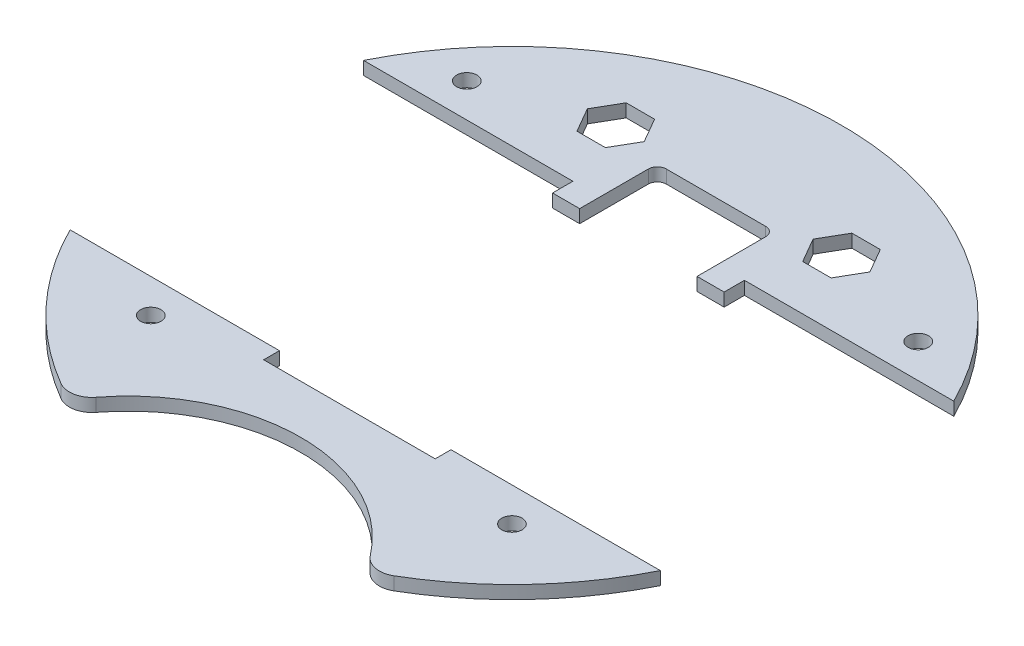
SolidWorks part; units mm, degrees
material "Acrylic (Medium-high impact)"
ref_plane "Front Plane" through (0, 0, 0) normal (0, 0, 1) x (1, 0, 0)
ref_plane "Top Plane" through (0, 0, 0) normal (0, 1, 0) x (1, 0, 0)
ref_plane "Right Plane" through (0, 0, 0) normal (1, 0, 0) x (0, 0, -1)
sketch "Sketch1" plane through (0, 0, 0) normal (0, 1, 0) x (1, 0, 0)
  line L0 (0, -85) -> (-32.7511, -65.2408) construction
  line L1 (0, -85) -> (0, 0) construction
  arc A0 (36.8566, -63.0126) -> (-36.8566, -63.0126) centre (0, 0) ccw
  arc A1 (30.3631, -61.7375) -> (-30.3631, -61.7375) centre (0, -85) ccw
  arc A2 (36.8566, -63.0126) -> (30.3631, -61.7375) centre (34.3322, -58.6967) cw
  arc A3 (-30.3631, -61.7375) -> (-36.8566, -63.0126) centre (-34.3322, -58.6967) cw
  dimension "D1" = 146
  dimension "D2" = 76.5
  dimension "D4" = 5
  dimension "D3" = 85
extrude "Boss-Extrude1" add sketch "Sketch1" along normal blind 2.9
sketch "solenoid placement" plane through (0, 2.9, 0) normal (0, 1, 0) x (1, 0, 0)
  line L4 (-19, -36) -> (19, -36)
  line L5 (-19, 28) -> (-19, -36)
  line L6 (19, 28) -> (-19, 28)
  line L7 (19, -36) -> (19, 28)
  line L8 (-19, -36) -> (19, -36)
  line L9 (-19, 28) -> (-19, -36)
  line L10 (19, 28) -> (-19, 28)
  line L11 (19, -36) -> (19, 28)
  dimension "D1" = 0
extrude "Cut-Extrude1" cut sketch "solenoid placement" against normal through all
sketch "Sketch5" plane through (0, 2.9, 0) normal (0, 1, 0) x (1, 0, 0)
  line L6 (-18.7069, 48) -> (-21.8534, 53.45)
  line L7 (-21.8534, 53.45) -> (-28.1466, 53.45)
  line L8 (-28.1466, 53.45) -> (-31.2931, 48)
  line L9 (-31.2931, 48) -> (-28.1466, 42.55)
  line L10 (-28.1466, 42.55) -> (-21.8534, 42.55)
  line L11 (-21.8534, 42.55) -> (-18.7069, 48)
  line L12 (-18.7069, 48) -> (-21.8534, 53.45)
  line L13 (-21.8534, 53.45) -> (-28.1466, 53.45)
  line L14 (-28.1466, 53.45) -> (-31.2931, 48)
  line L15 (-31.2931, 48) -> (-28.1466, 42.55)
  line L16 (-28.1466, 42.55) -> (-21.8534, 42.55)
  line L17 (-21.8534, 42.55) -> (-18.7069, 48)
  line L18 (18.7069, 48) -> (21.8534, 42.55)
  line L19 (21.8534, 53.45) -> (18.7069, 48)
  line L20 (28.1466, 53.45) -> (21.8534, 53.45)
  line L21 (31.2931, 48) -> (28.1466, 53.45)
  line L22 (28.1466, 42.55) -> (31.2931, 48)
  line L23 (21.8534, 42.55) -> (28.1466, 42.55)
  line L24 (18.7069, 48) -> (21.8534, 42.55)
  line L25 (21.8534, 53.45) -> (18.7069, 48)
  line L26 (28.1466, 53.45) -> (21.8534, 53.45)
  line L27 (31.2931, 48) -> (28.1466, 53.45)
  line L28 (28.1466, 42.55) -> (31.2931, 48)
  line L29 (21.8534, 42.55) -> (28.1466, 42.55)
  dimension "D1" = 0
  dimension "D2" = 0
extrude "Cut-Extrude5" cut sketch "Sketch5" against normal through all
sketch "Sketch6" plane through (0, 2.9, 0) normal (0, 1, 0) x (1, 0, 0)
  circle A0 centre (-50, 40) radius 2.25
  circle A1 centre (40, -40) radius 2.4
  circle A2 centre (40, -40) radius 2.4 construction
  circle A3 centre (-40, -40) radius 2.4
  circle A4 centre (-40, -40) radius 2.4 construction
  circle A5 centre (-50, 40) radius 2.4
  circle A6 centre (-50, 40) radius 2.4 construction
  circle A7 centre (50, 40) radius 2.4
  circle A8 centre (50, 40) radius 2.4 construction
  circle A9 centre (50, 40) radius 2.25
  circle A10 centre (40, -40) radius 2.25
  circle A11 centre (-40, -40) radius 2.25
  point P15 (0, 0)
  dimension "D5" = 4.5
extrude "Cut-Extrude6" cut sketch "Sketch6" against normal through all
sketch "Sketch3" plane through (0, 2.9, 0) normal (0, 1, 0) x (1, 0, 0)
  line L0 (-19, 28) -> (-19, 32.5)
  line L1 (73, -32.5) -> (-73, -32.5)
  line L2 (73, -32.5) -> (73, 32.5)
  line L3 (73, 32.5) -> (19, 32.5)
  line L4 (-73, -32.5) -> (-73, 32.5)
  line L5 (73, -32.5) -> (-73, 32.5) construction
  line L6 (73, 32.5) -> (-73, -32.5) construction
  line L7 (-19, 28) -> (19, 28)
  line L8 (19, 28) -> (19, 32.5)
  line L9 (-19, 32.5) -> (-73, 32.5)
  line L10 (-19, 28) -> (-19, -36) construction
  arc A0 (36.8566, -63.0126) -> (-36.8566, -63.0126) centre (0, 0) ccw construction
  point P0 (0, 0)
  point P10 (0, 0)
  point P13 (0, 0)
  point P14 (19, 28)
  point P19 (-19, 28)
  dimension "D1" = 65
extrude "Cut-Extrude3" cut sketch "Sketch3" against normal through all
sketch "Sketch7" plane through (0, 2.9, 0) normal (0, 1, 0) x (1, 0, 0)
  line L4 (-13, 28) -> (13, 28)
  line L5 (13, 28) -> (13, 43.2)
  line L6 (11, 45.2) -> (-11, 45.2)
  line L7 (-13, 43.2) -> (-13, 28)
  line L8 (-13, 28) -> (13, 28)
  line L9 (13, 28) -> (13, 43.2)
  line L10 (11, 45.2) -> (-11, 45.2)
  line L11 (-13, 43.2) -> (-13, 28)
  arc A2 (13, 43.2) -> (11, 45.2) centre (11, 43.2) ccw
  arc A3 (-11, 45.2) -> (-13, 43.2) centre (-11, 43.2) ccw
  arc A4 (13, 43.2) -> (11, 45.2) centre (11, 43.2) ccw
  arc A5 (-11, 45.2) -> (-13, 43.2) centre (-11, 43.2) ccw
  dimension "D1" = 0
extrude "Cut-Extrude7" cut sketch "Sketch7" against normal through all
equation "\"smallPulleyTeeth\"= 15"
equation "\"largePulleyTeeth\"= 30"
equation "\"eighthThick\"= 2.9mm"
equation "\"sixteenthThick\" = 1.7mm"
equation "\"quarterThick\"=6.0mm"
equation "\"OD\" = 146mm"
equation "\"puckAngle\" = 60.5deg"
equation "\"D1@Sketch1\"=\"OD\""
equation "\"puckDiam\" = 76.5mm"
equation "\"D2@Sketch1\"=\"puckDiam\""
equation "\"D1@Boss-Extrude1\"=\"eighthThick\""
equation "\"axlePress\" = 5.9mm"
equation "\"press\" = 0.2mm"
equation "\"wheelClear\" = 0.3mm"
equation "\"10-32clear\" = 4.8mm"
equation "\"6-32clear\" = 3.3mm"
equation "\"8-32clear\" = 4.0mm"
equation "\"wheelHeight\" = 22mm"
equation "\"wheelWell\" = 65mm"
equation "\"D1@Sketch3\"=\"wheelWell\""
equation "\"puckDist\" = 85mm"
equation "\"scoopFillet\" = 5mm"
equation "\"4-40clear\" = 3.0mm"
equation "\"D3@Sketch1\"=\"puckDist\""
equation "\"D4@Sketch1\"=\"scoopFillet\""
equation "\"10-32tap\" = 4.5mm"
equation "\"D5@Sketch6\"=\"10-32tap\""
